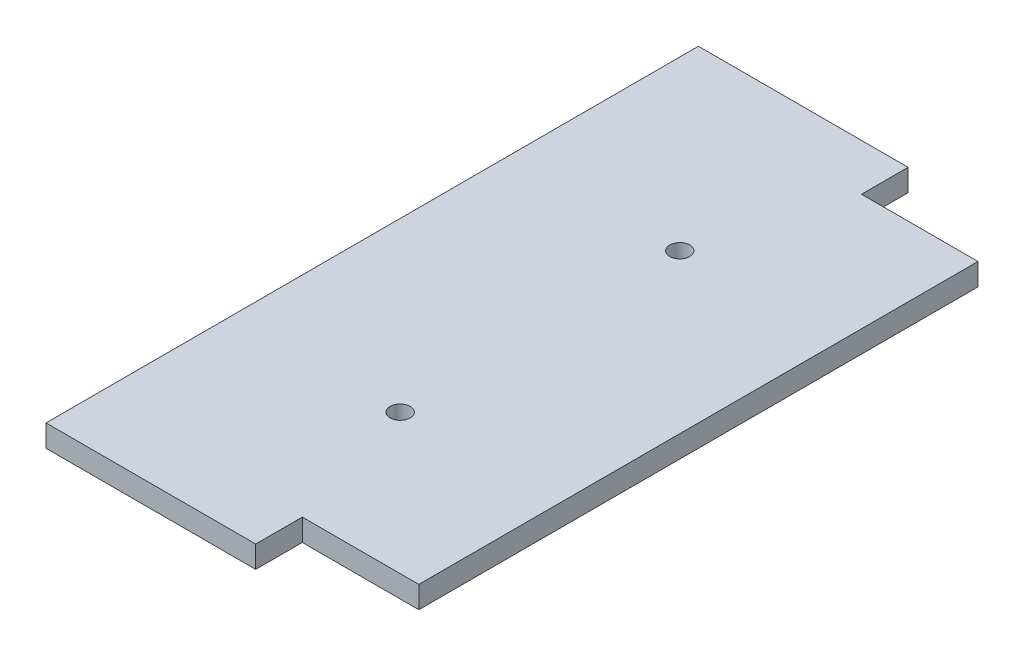
SolidWorks part; units mm, degrees
ref_plane "Front Plane" through (0, 0, 0) normal (0, 0, 1) x (1, 0, 0)
ref_plane "Top Plane" through (0, 0, 0) normal (0, 1, 0) x (1, 0, 0)
ref_plane "Right Plane" through (0, 0, 0) normal (1, 0, 0) x (0, 0, -1)
sketch "Sketch2" plane through (0, 0, 0) normal (0, 1, 0) x (1, 0, 0)
  line L0 (57.15, 177.8) -> (88.9, 177.8) construction
  line L1 (0, 0) -> (57.15, 0)
  line L2 (0, 0) -> (0, 177.8)
  line L3 (0, 177.8) -> (57.15, 177.8)
  line L4 (88.9, 12.7) -> (88.9, 165.1)
  line L5 (88.9, 177.8) -> (57.15, 177.8) construction
  line L6 (88.9, 177.8) -> (88.9, 165.1) construction
  line L7 (88.9, 165.1) -> (57.15, 165.1)
  line L8 (57.15, 177.8) -> (57.15, 165.1)
  line L9 (88.9, 165.1) -> (88.9, 177.8) construction
  line L10 (-1000, 88.9) -> (49000, 88.9) construction
  line L11 (57.15, 0) -> (57.15, 12.7)
  line L12 (88.9, 12.7) -> (57.15, 12.7)
  line L13 (57.15, 0) -> (88.9, 0) construction
  line L14 (88.9, 0) -> (88.9, 12.7) construction
  point P11 (0, 88.9)
  dimension "D1" = 177.8
  dimension "D2" = 88.9
  dimension "D3" = 31.75
  dimension "D4" = 12.7
extrude "Boss-Extrude1" add sketch "Sketch2" along normal blind 5.9944 contours L3 L8 L7 L4 L12 L11 L1 L2
sketch "Sketch4" plane through (0, 5.9944, 0) normal (0, 1, 0) x (1, 0, 0)
  line L0 (0, 0) -> (0, 177.8) construction
  line L2 (45.72, 127) -> (45.72, 50.8) construction
  circle A0 centre (45.72, 127) radius 2.7305
  circle A1 centre (45.72, 50.8) radius 2.7305
  point P4 (45.72, 88.9)
  point P6 (0, 0)
  point P12 (0, 88.9)
  dimension "D3" = 5.461
  dimension "D4" = 5.461
  dimension "D1" = 76.2
  dimension "D2" = 45.72
extrude "Cut-Extrude2" cut sketch "Sketch4" against normal through all both
equation "\"threaded_insert_hole\"=0.1472"
equation "\"th\"=1.25249"
